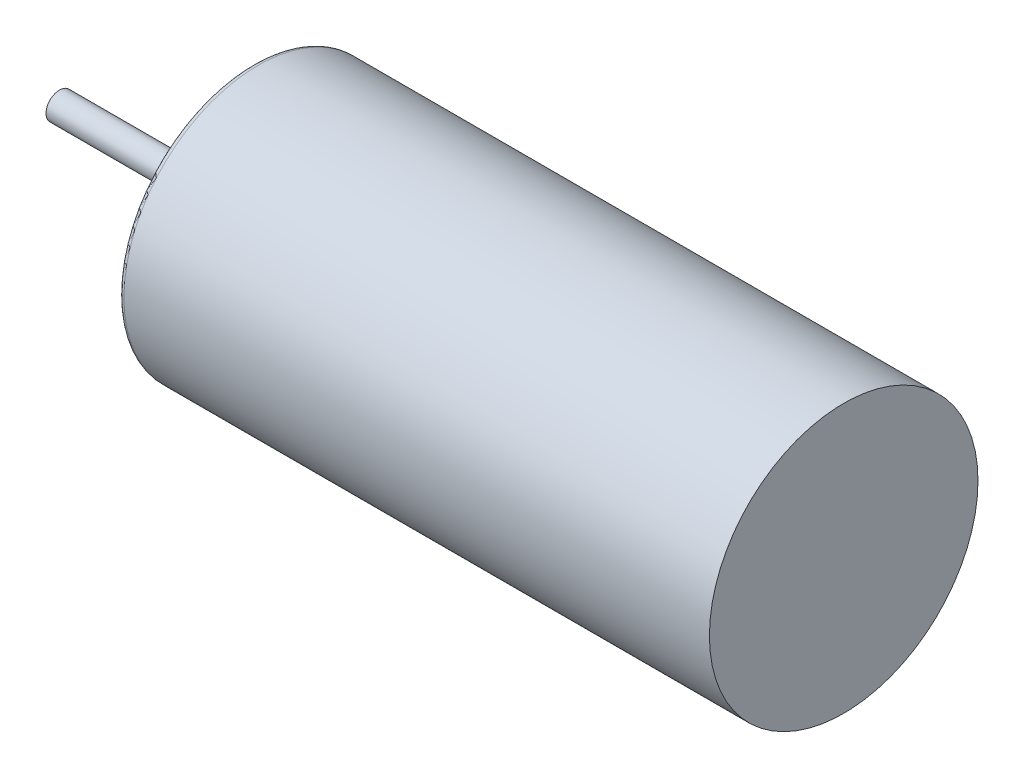
SolidWorks part; units mm, degrees
ref_plane "Plano frontal" through (0, 0, 0) normal (0, 0, 1) x (1, 0, 0)
ref_plane "Plano superior" through (0, 0, 0) normal (0, 1, 0) x (1, 0, 0)
ref_plane "Plano direito" through (0, 0, 0) normal (1, 0, 0) x (0, 0, -1)
sketch "Esboço2" plane through (0, 0, 0) normal (1, 0, 0) x (0, 0, -1)
  circle A0 centre (0, 0) radius 5
  dimension "D1" = 10
extrude "Ressalto-extrusão1" add sketch "Esboço2" against normal blind 22
sketch "Esboço3" plane through (-22, 0, 0) normal (-1, 0, 0) x (0, 0, 1)
  circle A0 centre (0, 0) radius 0.5
  dimension "D1" = 1
extrude "Ressalto-extrusão2" add sketch "Esboço3" along normal blind 7.2
sketch "Esboço4" plane through (-22, 0, 0) normal (-1, 0, 0) x (0, 0, 1)
  circle A0 centre (0, 0) radius 1
  dimension "D1" = 2
extrude "Ressalto-extrusão3" add sketch "Esboço4" along normal blind 0.5
fillet "Filete1" radius 0.2 1 edges at (-22, 0, -5)
